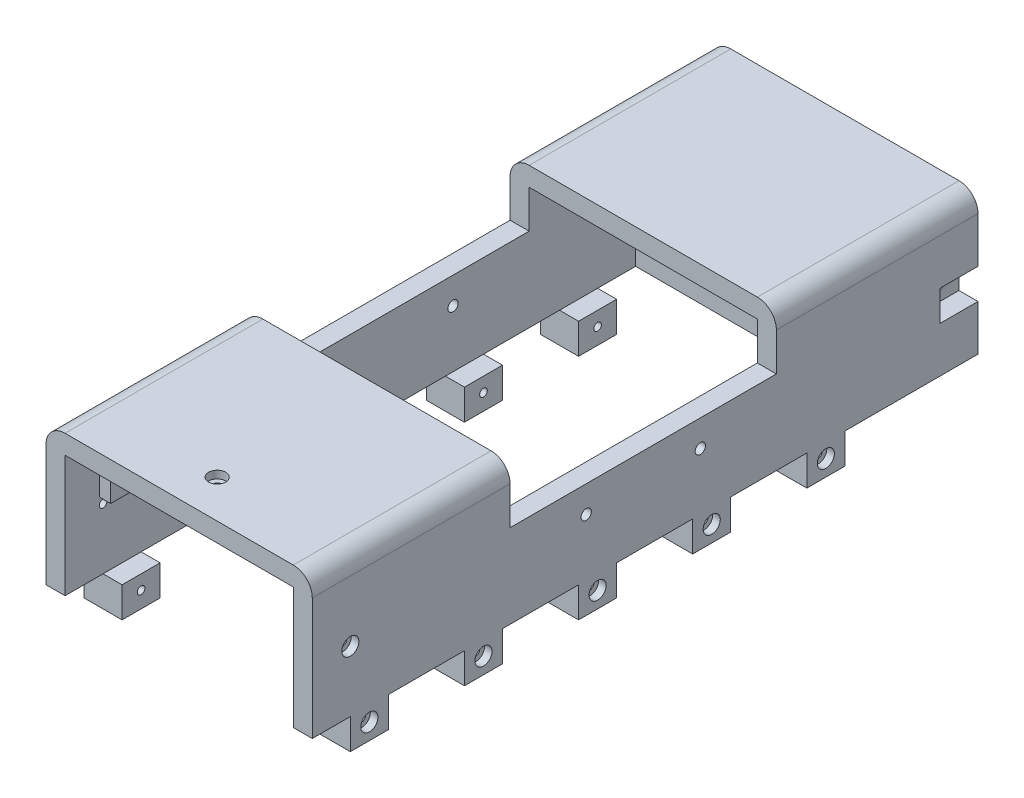
SolidWorks part; units mm, degrees
material "LW PLA"
ref_plane "Front Plane" through (0, 0, 0) normal (0, 0, 1) x (1, 0, 0)
ref_plane "Top Plane" through (0, 0, 0) normal (0, 1, 0) x (1, 0, 0)
ref_plane "Right Plane" through (0, 0, 0) normal (1, 0, 0) x (0, 0, -1)
sketch "Sketch1" plane through (0, 0, 0) normal (0, 1, 0) x (1, 0, 0)
  line L0 (-25, 0) -> (25, 0)
  line L1 (35, -185) -> (35, -10)
  line L2 (0, -25) -> (35, -25) construction
  line L3 (0, -35) -> (35, -35) construction
  line L4 (0, -95) -> (35, -95) construction
  line L5 (0, -175) -> (35, -175) construction
  line L6 (0, -20.35) -> (0, 20.35) construction
  line L7 (-35, -185) -> (-35, -10)
  line L8 (30, -185) -> (30, -10) construction
  line L9 (-30, -185) -> (-30, -10) construction
  arc A0 (35, -10) -> (25, 0) centre (25, -10) ccw
  arc A1 (-35, -10) -> (-25, 0) centre (-25, -10) cw
  point P20 (0, 0)
  dimension "D1" = 10
  dimension "D2" = 175
  dimension "D3" = 25
  dimension "D4" = 10
  dimension "D5" = 60
  dimension "D6" = 80
  dimension "D7" = 25
  dimension "D8" = 5
ref_plane "STA1" through (0, 0, 10) normal (0, 0, 1) x (1, 0, 0)
sketch "Body Arch" plane through (0, 0, 10) normal (0, 0, 1) x (1, 0, 0)
  line L0 (-30, 32) -> (30, 32)
  line L1 (-35, 0) -> (-30, 0)
  line L2 (-35, 0) -> (-35, 32)
  line L3 (-30, 37) -> (30, 37)
  line L4 (35, 0) -> (35, 32)
  line L5 (30, 0) -> (30, 32)
  line L7 (-30, 0) -> (-30, 32)
  line L8 (-30, 5) -> (30, 5) construction
  line L9 (-30, 5) -> (-30, 32) construction
  line L10 (30, 5) -> (30, 32) construction
  line L11 (30, 0) -> (35, 0)
  line L13 (-35, 0) -> (35, 0) construction
  arc A0 (35, 32) -> (30, 37) centre (30, 32) ccw
  arc A1 (-35, 32) -> (-30, 37) centre (-30, 32) cw
  arc A2 (30, 32) -> (30, 32) centre (30, 32) ccw
  arc A3 (-30, 32) -> (-30, 32) centre (-30, 32) cw
  point P9 (-35, 37)
  dimension "D2" = 5
  dimension "D1" = 37
  dimension "D3" = 5
sketch "Bulkhead" plane through (0, 0, 0) normal (0, 1, 0) x (1, 0, 0)
  line L0 (0, -35) -> (35, -35) construction
  line L1 (-30, -185) -> (-30, -10) construction
  line L2 (-30, -25) -> (30, -25)
  line L3 (-30, -25) -> (-30, -35)
  line L4 (-30, -35) -> (30, -35)
  line L5 (30, -25) -> (30, -35)
  line L6 (30, -185) -> (30, -10) construction
extrude "Boss-Extrude1" add sketch "Body Arch" along normal up to vertex (175 mm away) up to point (-35, 0, 185)
ref_plane "Plane1" through (35, 0, 0) normal (1, 0, 0) x (0, 0, -1)
sketch "Sketch2" plane through (35, 0, 0) normal (1, 0, 0) x (0, 0, -1)
  line L0 (-185, 0) -> (-10, 0) construction
  line L1 (-175, 0) -> (-165, 0)
  line L2 (-175, 0) -> (-175, -8)
  line L3 (-175, -8) -> (-165, -8)
  line L4 (-165, 0) -> (-165, -8)
  line L6 (-185, 0) -> (-10, 0) construction
  line L7 (-145, 0) -> (-145, -8)
  line L8 (-145, 0) -> (-135, 0)
  line L9 (-135, 0) -> (-135, -8)
  line L10 (-145, -8) -> (-135, -8)
  line L11 (-115, 0) -> (-115, -8)
  line L12 (-115, 0) -> (-105, 0)
  line L13 (-105, 0) -> (-105, -8)
  line L14 (-115, -8) -> (-105, -8)
  line L15 (-85, 0) -> (-85, -8)
  line L16 (-85, 0) -> (-75, 0)
  line L17 (-75, 0) -> (-75, -8)
  line L18 (-85, -8) -> (-75, -8)
  line L19 (-55, 0) -> (-55, -8)
  line L20 (-55, 0) -> (-45, 0)
  line L21 (-45, 0) -> (-45, -8)
  line L22 (-55, -8) -> (-45, -8)
  circle A0 centre (-170, -3.75) radius 1
  circle A1 centre (-170, -3.75) radius 2.25
  circle A2 centre (-140, -3.75) radius 2.25
  circle A3 centre (-140, -3.75) radius 1
  circle A4 centre (-110, -3.75) radius 2.25
  circle A5 centre (-110, -3.75) radius 1
  circle A6 centre (-80, -3.75) radius 2.25
  circle A7 centre (-80, -3.75) radius 1
  circle A8 centre (-50, -3.75) radius 2.25
  circle A9 centre (-50, -3.75) radius 1
  point P12 (-170, 0)
  dimension "D4" = 2
  dimension "D6" = 4.5
  dimension "D1" = 10
  dimension "D2" = 8
  dimension "D3" = 10
  dimension "D5" = 3.75
  dimension "D7" = 5
extrude "Boss-Extrude2" add sketch "Sketch2" against normal blind 10 contours L4 L1 L2 L3 A1 | L7 L10 L9 L8 A2 | L11 L14 L13 L12 A4 | L15 L18 L17 L16 A6 | L19 L22 L21 L20 A8 | A1 A0 | A2 A3 | A4 A5 | A6 A7 | A8 A9 region at (35, -0.1281, 170) region at (35, -0.1281, 140) region at (35, -0.1281, 110) region at (35, -0.1281, 80) region at (35, -0.1281, 50) region at (35, -3.75, 172.1864) region at (35, -3.75, 142.1864) region at (35, -3.75, 112.1864) region at (35, -3.75, 82.1864) region at (35, -3.75, 52.1864)
extrude "Cut-Extrude1" cut sketch "Sketch2<3>" against normal blind 2 contours A1 A0 | A2 A3 | A4 A5 | A6 A7 | A8 A9 region at (35, -3.75, 172.1864) region at (35, -3.75, 142.1864) region at (35, -3.75, 112.1864) region at (35, -3.75, 82.1864) region at (35, -3.75, 52.1864)
sketch "Sketch2<3>" plane through (35, 0, 0) normal (1, 0, 0) x (0, 0, -1) same geometry as "Sketch2"
mirror "Mirror1" about plane through (0, 0, 0) normal (1, 0, 0) of "Cut-Extrude1", "Boss-Extrude2"
sketch "Sketch4" plane through (30, 0, 0) normal (-1, 0, 0) x (0, 0, 1)
  line L0 (10, 32) -> (10, 0) construction
  line L1 (10, 22) -> (22, 22)
  line L2 (10, 22) -> (10, 10)
  line L3 (10, 10) -> (22, 10)
  line L4 (22, 22) -> (22, 10)
  circle A1 centre (15, 16) radius 1.35
  point P6 (10, 16)
  point P7 (10, 16)
  point P13 (22, 16)
  dimension "D3" = 2.7
  dimension "D1" = 12
  dimension "D2" = 12
  dimension "D4" = 5
extrude "Boss-Extrude3" add sketch "Sketch4" along normal blind 5
sketch "Sketch6" plane through (0, 0, 10) normal (0, 0, -1) x (-1, 0, 0)
  line L0 (-35, 0) -> (-35, 32) construction
  line L1 (-35, 20) -> (-30, 20)
  line L2 (-35, 20) -> (-35, 12)
  line L3 (-35, 12) -> (-30, 12)
  line L4 (-30, 20) -> (-30, 12)
  point P6 (-35, 16)
  point P7 (-35, 16)
  dimension "D1" = 5
  dimension "D2" = 8
extrude "Cut-Extrude4" cut sketch "Sketch6" against normal blind 10
mirror "Mirror2" about plane through (0, 0, 0) normal (1, 0, 0) of "Cut-Extrude4", "Boss-Extrude3"
ref_plane "Plane2" through (0, 37, 0) normal (0, 1, 0) x (1, 0, 0)
sketch "Sketch7" plane through (0, 37, 0) normal (0, 1, 0) x (1, 0, 0)
  line L0 (-35, -185) -> (-35, -10) construction
  line L1 (-35, -63) -> (35, -63)
  line L2 (-35, -63) -> (-35, -133)
  line L3 (-35, -133) -> (35, -133)
  line L4 (35, -63) -> (35, -133)
  line L5 (35, -185) -> (35, -10) construction
  line L6 (30, -185) -> (-30, -185) construction
  dimension "D1" = 70
  dimension "D2" = 52
extrude "Cut-Extrude5" cut sketch "Sketch7" against normal blind 15
sketch "Sketch9" plane through (35, 0, 0) normal (1, 0, 0) x (0, 0, -1)
  line L0 (-133, 22) -> (-63, 22) construction
  circle A0 centre (-83, 15) radius 1.35
  circle A4 centre (-113, 15) radius 1.35
  dimension "D3" = 2.7
  dimension "D4" = 2
  dimension "D1" = 7
  dimension "D2" = 20
extrude "Cut-Extrude6" cut sketch "Sketch9" against normal up to next contours A0 | A4
mirror "Mirror4" about plane through (0, 0, 0) normal (1, 0, 0) of "Cut-Extrude6"
sketch "Sketch10" plane through (0, 0, 0) normal (1, 0, 0) x (0, 0, -1)
  line L0 (-185, 32) -> (-195, 32)
  line L1 (-185, 32) -> (-165, 32)
  line L3 (-185, 27) -> (-165, 27)
  line L4 (-165, 32) -> (-165, 27)
  line L6 (-195, 32) -> (-195, 27)
  line L7 (-195, 27) -> (-185, 27)
  dimension "D1" = 20
  dimension "D2" = 5
  dimension "D3" = 10
sketch "Sketch13" plane through (-30, 0, 0) normal (1, 0, 0) x (0, 0, -1)
  line L5 (-185, 0) -> (-185, 32) construction
  line L10 (-185, 26) -> (-165, 26)
  line L11 (-185, 26) -> (-185, 6)
  line L12 (-185, 6) -> (-165, 6)
  line L13 (-165, 26) -> (-165, 6)
  line L15 (-185, 26) -> (-195, 26)
  line L16 (-185, 26) -> (-185, 6)
  line L17 (-185, 6) -> (-195, 6)
  line L18 (-195, 26) -> (-195, 6)
  point P6 (-185, 16)
  point P7 (-185, 16)
  dimension "D1" = 20
  dimension "D2" = 20
  dimension "D3" = 10
sketch "Sketch17" plane through (0, 37, 0) normal (0, 1, 0) x (1, 0, 0)
  line L0 (30, -185) -> (-30, -185) construction
  circle A0 centre (0, -175) radius 1
  circle A1 centre (0, -175) radius 2.25
  point P6 (0, -185)
  dimension "D1" = 2
  dimension "D2" = 4.5
  dimension "D3" = 10
sketch "Sketch18" plane through (35, 0, 0) normal (1, 0, 0) x (0, 0, -1)
  line L0 (-185, 26) -> (-185, 6) construction
  circle A0 centre (-175, 16) radius 1
  circle A1 centre (-175, 16) radius 2.25
  point P6 (-185, 16)
  dimension "D1" = 10
extrude "Cut-Extrude13" cut sketch "Sketch17" against normal up to next contours A0
extrude "Cut-Extrude14" cut sketch "Sketch17<4>" against normal blind 2 contours A1
sketch "Sketch17<4>" plane through (0, 37, 0) normal (0, 1, 0) x (1, 0, 0) same geometry as "Sketch17"
extrude "Cut-Extrude15" cut sketch "Sketch18" against normal up to next contours A0
extrude "Cut-Extrude16" cut sketch "Sketch18<3>" against normal blind 2 contours A1
sketch "Sketch18<3>" plane through (35, 0, 0) normal (1, 0, 0) x (0, 0, -1) same geometry as "Sketch18"
mirror "Mirror6" about plane through (0, 0, 0) normal (1, 0, 0) of "Cut-Extrude15", "Cut-Extrude16"
extrude "Boss-Extrude4" add sketch "Bulkhead" along normal up to next
sketch "Sketch20" plane through (-35, 0, 0) normal (-1, 0, 0) x (0, 0, 1)
  line L0 (133, 22) -> (133, 32) construction
  line L1 (138, 32) -> (171, 32)
  line L2 (138, 32) -> (138, 20)
  line L3 (138, 20) -> (171, 20)
  line L4 (171, 32) -> (171, 20)
  line L5 (185, 32) -> (133, 32) construction
  point P6 (0, 0)
  dimension "D1" = 33
  dimension "D2" = 12
  dimension "D3" = 5
extrude "Cut-Extrude17" cut sketch "Sketch20" against normal up to next
sketch "Sketch21" plane through (-30, 0, 0) normal (1, 0, 0) x (0, 0, -1)
  line L0 (-170.8, 26) -> (-138.2, 26) construction
  line L1 (-171, 20) -> (-138, 20) construction
  line L2 (-171, 32) -> (-171, 20) construction
  line L3 (-154.5, 26) -> (-154.5, 20) construction
  line L4 (-133, 32) -> (-143.1, 32)
  line L5 (-133, 32) -> (-133, 18)
  line L6 (-133, 18) -> (-143.1, 18)
  line L7 (-143.1, 32) -> (-143.1, 18)
  line L8 (-176, 18) -> (-165.9, 18)
  line L9 (-165.9, 32) -> (-165.9, 18)
  line L10 (-176, 32) -> (-165.9, 32)
  line L11 (-176, 32) -> (-176, 18)
  circle A0 centre (-140.2, 26) radius 1
  circle A1 centre (-168.8, 26) radius 1
  point P4 (-154.5, 20)
  point P5 (-154.5, 26)
  point P8 (-171, 26)
  dimension "D4" = 2
  dimension "D1" = 32.6
  dimension "D2" = 4.9
  dimension "D3" = 2
  dimension "D5" = 28.6
  dimension "D6" = 14
extrude "Boss-Extrude6" add sketch "Sketch21" along normal blind 3
mirror "Mirror7" about plane through (0, 0, 0) normal (1, 0, 0) of "Boss-Extrude6"
